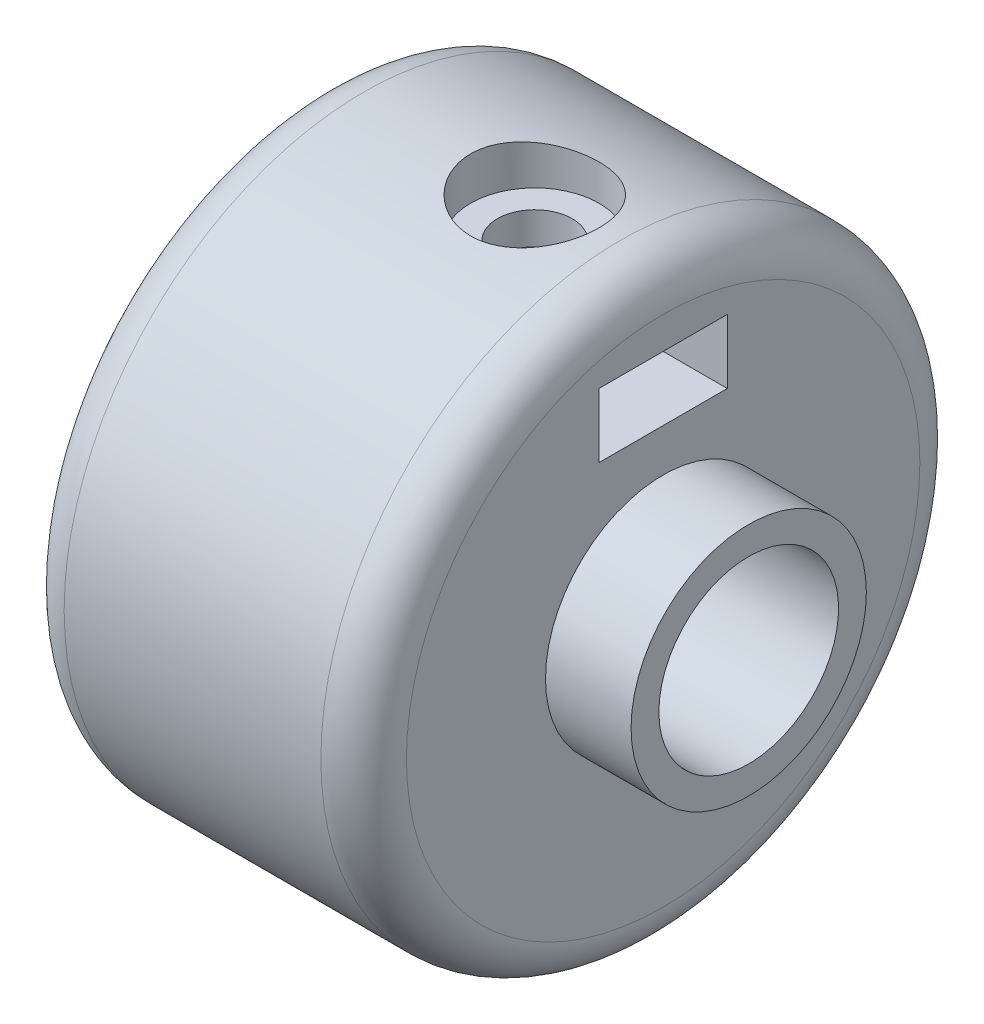
SolidWorks part; units mm, degrees
ref_plane "前视基准面" through (0, 0, 0) normal (0, 0, 1) x (1, 0, 0)
ref_plane "上视基准面" through (0, 0, 0) normal (0, 1, 0) x (1, 0, 0)
ref_plane "右视基准面" through (0, 0, 0) normal (1, 0, 0) x (0, 0, -1)
sketch "草图1" plane through (0, 0, 0) normal (0, 0, 1) x (1, 0, 0)
  line L0 (-12.0159, 0) -> (12.7091, 0) construction
  line L1 (0, 0) -> (0, 10.5504) construction
  line L2 (-15, 4.2) -> (0, 4.2)
  line L3 (-15, 4.2) -> (-15, 0)
  line L4 (-20, 0) -> (-15, 0)
  line L5 (0, 5.5) -> (-4, 5.5)
  line L6 (-4, 5.5) -> (-4, 14)
  line L7 (-4, 14) -> (-20, 14)
  line L8 (0, 5.5) -> (0, 4.2)
  line L9 (-20, 14) -> (-20, 0)
  dimension "D1" = 4.2
  dimension "D2" = 14
  dimension "D3" = 5.5
  dimension "D4" = 4
  dimension "D5" = 15
  dimension "D6" = 5
revolve "旋转1" add sketch "草图1" angle 360 about L0
sketch "草图2" plane through (0, 0, 0) normal (0, 1, 0) x (1, 0, 0)
  line L0 (0, 0) -> (-23.5637, 0) construction
  circle A0 centre (-10, 0) radius 1.75
  circle A1 centre (-10, 0) radius 3
  dimension "D1" = 3.5
  dimension "D2" = 6
  dimension "D3" = 10
extrude "切除-拉伸5" cut sketch "草图2" along normal through all contours A0
extrude "切除-拉伸6" cut sketch "草图2<4>" against normal blind 2 from offset 14 contours A1
sketch "草图2<4>" plane through (0, 0, 0) normal (0, 1, 0) x (1, 0, 0) same geometry as "草图2"
sketch "草图4" plane through (0, 0, 0) normal (1, 0, 0) x (0, 0, -1)
  line L0 (0, 0) -> (0, 14.6396) construction
  line L2 (-3, 10.5) -> (3, 10.5)
  line L3 (-3, 10.5) -> (-3, 7.5)
  line L4 (-3, 7.5) -> (3, 7.5)
  line L5 (3, 10.5) -> (3, 7.5)
  line L6 (-3, 10.5) -> (3, 7.5) construction
  line L7 (-3, 7.5) -> (3, 10.5) construction
  point P1 (0, 9)
  dimension "D1" = 3
  dimension "D2" = 6
  dimension "D3" = 9
extrude "切除-拉伸7" cut sketch "草图4" against normal blind 15
fillet "圆角1" radius 2 2 edges at (-20, 0, 14) (-4, 0, 14)
